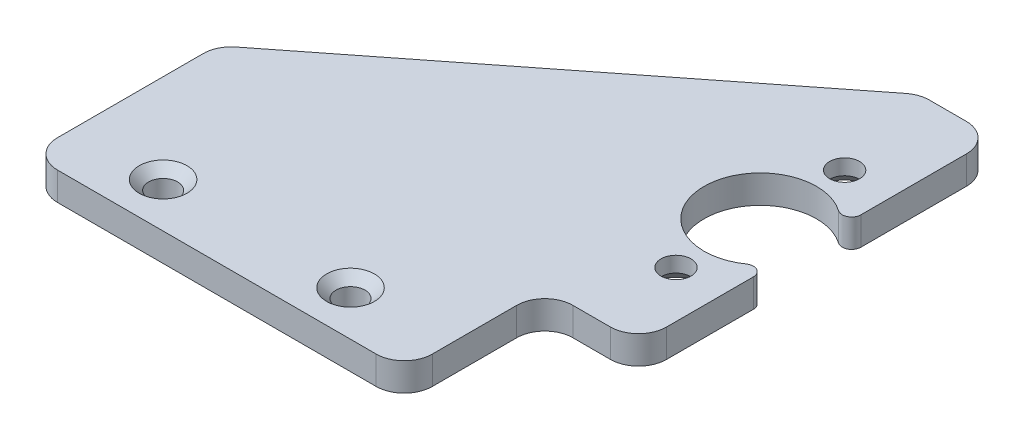
SolidWorks part; units mm, degrees
ref_plane "Plano frontal" through (0, 0, 0) normal (0, 0, 1) x (1, 0, 0)
ref_plane "Plano superior" through (0, 0, 0) normal (0, 1, 0) x (1, 0, 0)
ref_plane "Plano direito" through (0, 0, 0) normal (1, 0, 0) x (0, 0, -1)
sketch "Esboço1" plane through (0, 0, 0) normal (0, 1, 0) x (1, 0, 0)
  line L0 (0, 0) -> (25, 0) construction
  line L1 (0, 0) -> (0, 20) construction
  line L2 (-25, 20) -> (25, 20)
  line L5 (25, -20) -> (-25, -20)
  line L6 (-25, -20) -> (-25, 20)
  line L7 (25, 20) -> (25, -20)
  line L8 (25, 0.0001) -> (24.9995, 0.0001)
  line L9 (24.9995, -0.0001) -> (25, -0.0001)
  line L10 (24.9995, 0.0001) -> (24.9995, -0.0001)
  line L11 (25, -0.0001) -> (25, 0.0001)
  circle A0 centre (20, 9) radius 1.6
  circle A1 centre (20, -9) radius 1.6
  circle A2 centre (20, 0) radius 6
  point P3 (-25, 0)
  point P7 (0, 20)
  dimension "D4" = 3.2
  dimension "D6" = 12
  dimension "D1" = 50
  dimension "D2" = 40
  dimension "D3" = 0
  dimension "D5" = 18
  dimension "D7" = 5
  dimension "D8" = 5
extrude "Ressalto-extrusão10" add sketch "Esboço1" along normal blind 3 contours A2 L7 L2 L6 L5 A1 A0 region at (-1.3167, 0, 0)
fillet "Filete2" radius 1 2 edges at (25, 1.5, -3.3166) (25, 1.5, 3.3166)
chamfer "Chanfro1" distance 1.35 angle 45 2 edges at (20, 0, -7.4) (20, 0, 10.6)
sketch "Esboço5" plane through (0, 0, 0) normal (0, -1, 0) x (1, 0, 0)
  line L0 (-25, 20) -> (-25, 33)
  line L1 (-25, 33) -> (25, 33)
  line L2 (25, 33) -> (25, 20)
  line L3 (25, 20) -> (-25, 20)
  dimension "D1" = 13
extrude "Ressalto-extrusão13" add sketch "Esboço5" against normal blind 3
sketch "Esboço7" plane through (0, 0, 0) normal (0, -1, 0) x (1, 0, 0)
  line L0 (25, 5.7446) -> (25, 6.7446)
  line L1 (25, 5.7446) -> (25, 33) construction
  line L2 (25, 6.7446) -> (-25, 6.7446) construction
  line L3 (-25, 33) -> (-25, -20) construction
  line L4 (14, 0) -> (10, 0)
  line L5 (-15.5, 28.2346) -> (4.5, 28.2346) construction
  circle A0 centre (-15.5, 28.2346) radius 1.55
  circle A1 centre (4.5, 28.2346) radius 1.55
  arc A2 (23.4286, 4.9239) -> (23.4286, -4.9239) centre (20, 0) ccw construction
  dimension "D2" = 3.1
  dimension "D1" = 1
  dimension "D3" = 20
  dimension "D4" = 4
  dimension "D5" = 21.49
  dimension "D6" = 21.49
  dimension "D7" = 5.5
extrude "Corte-extrusão1" cut sketch "Esboço7" against normal through all contours A0 | A1
sketch "Esboço8" plane through (0, 0, 0) normal (0, -1, 0) x (1, 0, 0)
  line L0 (-25, -20) -> (-25, 13)
  line L1 (-25, 33) -> (-25, -20) construction
  line L2 (-25, 13) -> (17, -20)
  line L3 (-25, -20) -> (25, -20) construction
  line L4 (17, -20) -> (-25, -20)
  line L5 (25, 33) -> (25, 18)
  line L6 (25, 5.7446) -> (25, 33) construction
  line L7 (25, 18) -> (15, 18)
  line L8 (15, 18) -> (15, 33)
  line L9 (25, 33) -> (-25, 33) construction
  line L10 (15, 33) -> (25, 33)
  dimension "D1" = 20
  dimension "D2" = 8
  dimension "D3" = 15
  dimension "D4" = 10
extrude "Corte-extrusão2" cut sketch "Esboço8" against normal through all contours L4 L0 L2 | L10 L5 L7 L8
fillet "Filete3" radius 3 7 edges at (15, 1.5, 18) (-25, 1.5, 13) (-25, 1.5, 33) (15, 1.5, 33) (25, 1.5, 18) (25, 1.5, -20) (17, 1.5, -20)
chamfer "Chanfro2" distance 1 angle 45 2 edges at (4.5, 3, 26.6846) (-15.5, 3, 26.6846)
sketch "Esboço9" plane through (0, 0, 0) normal (0, -1, 0) x (1, 0, 0)
  line L0 (-15.5, 28.2346) -> (4.5, 28.2346) construction
  line L1 (-5.5, 28.2346) -> (-5.5, 10.2346) construction
  circle A0 centre (-5.5, 10.2346) radius 4
  dimension "D1" = 8
  dimension "D2" = 18
extrude "Ressalto-extrusão14" add sketch "Esboço9" along normal blind 8
